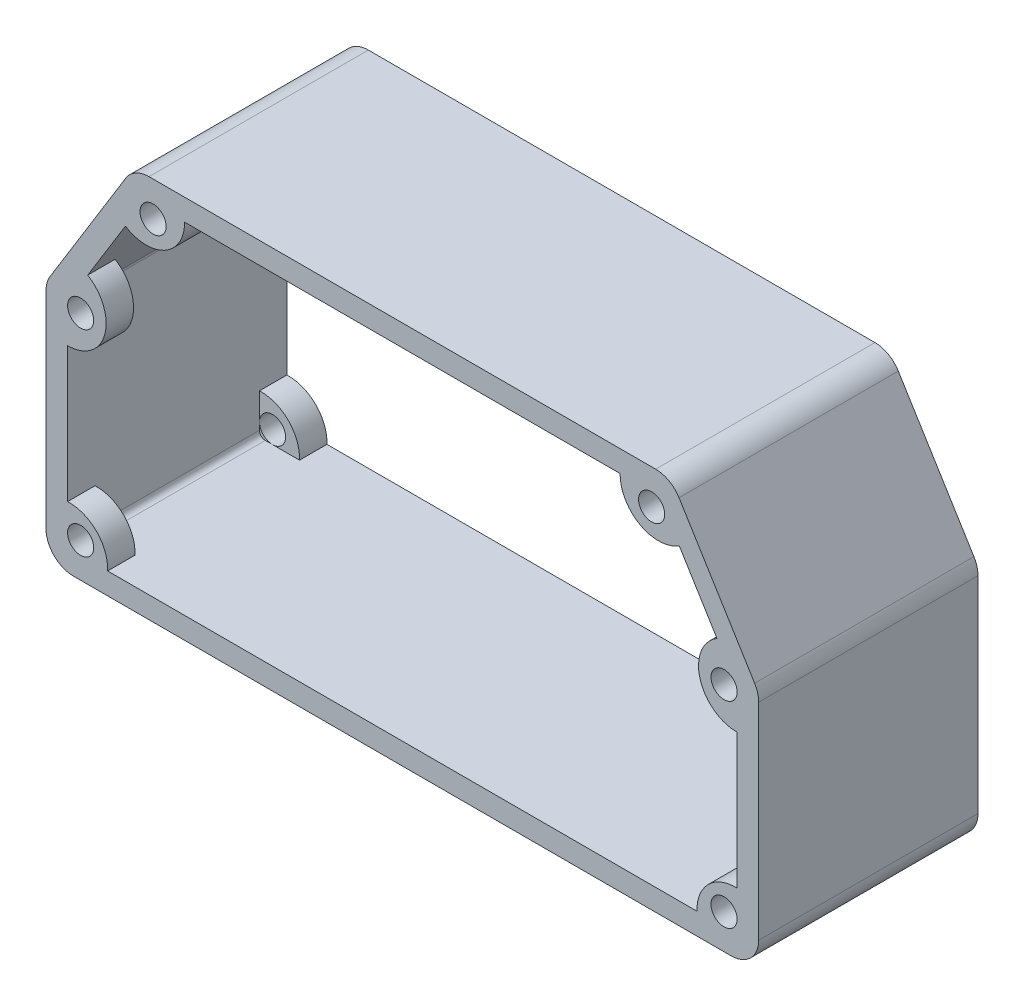
SolidWorks part; units mm, degrees
material "Custom Plastic"
ref_plane "X-Y Datum" through (0, 0, 0) normal (0, 0, 1) x (1, 0, 0)
ref_plane "X-Z Datum" through (0, 0, 0) normal (0, 1, 0) x (1, 0, 0)
ref_plane "Y-Z Datum" through (0, 0, 0) normal (1, 0, 0) x (0, 0, -1)
sketch "Sketch1" plane through (0, 0, 0) normal (0, 0, 1) x (1, 0, 0)
  line L0 (-82.55, -44.45) -> (-75.1791, 44.45)
  line L1 (-82.55, 44.45) -> (82.55, 44.45)
  line L2 (-82.55, 44.45) -> (-82.55, -44.45)
  line L3 (-82.55, -44.45) -> (82.55, -44.45)
  line L4 (82.55, 44.45) -> (82.55, -44.45)
  line L5 (-82.55, 44.45) -> (82.55, -44.45) construction
  line L6 (-82.55, -44.45) -> (82.55, 44.45) construction
  line L8 (0, 90.3576) -> (0, -90.3576) construction
  line L9 (82.55, -44.45) -> (75.1791, 44.45)
  point P0 (0, 0)
  point P12 (0, 0)
  dimension "D1" = 165.1
  dimension "D2" = 88.9
extrude "Boss-Extrude1" add sketch "Sketch1" along normal blind 50.8 contours L3 L9 L1 L0 | L1 L2 L0 | L9 L4 L1 region at (-80.093, 14.8167, 0) region at (0, -0.6924, 0) region at (80.093, 14.8167, 0)
sketch "Sketch2" plane through (0, 0, 0) normal (0, 0, -1) x (-1, 0, 0)
  line L0 (-82.55, 11.43) -> (-62.23, 44.45)
  line L1 (-82.55, 44.45) -> (-82.55, -44.45) construction
  line L2 (82.55, 44.45) -> (-82.55, 44.45) construction
  line L3 (0, -14.0019) -> (0, 14.0019) construction
  line L4 (82.55, 11.43) -> (62.23, 44.45)
  point P11 (0, 0)
  line M3 (-82.55, 44.45) -> (-82.55, -44.45)
  line M5 (82.55, -44.45) -> (82.55, 44.45)
  line M6 (82.55, 44.45) -> (-82.55, 44.45)
  dimension "D1" = 55.88
  dimension "D2" = 20.32
extrude "Cut-Extrude1" cut sketch "Sketch2" against normal through all contours L0 M3 M6 | L4 M5 M6 region at (75.7767, 33.4433, 0) region at (-75.7767, 33.4433, 0)
fillet "Fillet1" radius 6.35 6 edges at (82.55, -44.45, 25.4) (82.55, 11.43, 25.4) (62.23, 44.45, 25.4) (-62.23, 44.45, 25.4) (-82.55, 11.43, 25.4) (-82.55, -44.45, 25.4)
shell "Shell1" thickness 5 removed face at (0, 4.2293, 0)
sketch "Sketch4" plane through (0, 0, 45.8) normal (0, 0, -1) x (-1, 0, 0)
  line L6 (-59.8314, 38.8075) -> (-77.3497, 10.3402)
  line L7 (-77.55, 9.6327) -> (-77.55, -38.1)
  line L8 (-76.2, -39.45) -> (76.2, -39.45)
  line L9 (77.55, -38.1) -> (77.55, 9.6327)
  line L10 (77.3497, 10.3402) -> (59.8314, 38.8075)
  line L11 (58.6817, 39.45) -> (-58.6817, 39.45)
  line L12 (-59.8314, 38.8075) -> (-77.3497, 10.3402)
  line L13 (-77.55, 9.6327) -> (-77.55, -38.1)
  line L14 (-76.2, -39.45) -> (76.2, -39.45)
  line L15 (77.55, -38.1) -> (77.55, 9.6327)
  line L16 (77.3497, 10.3402) -> (59.8314, 38.8075)
  line L17 (58.6817, 39.45) -> (-58.6817, 39.45)
  arc A6 (76.2, -39.45) -> (77.55, -38.1) centre (76.2, -38.1) ccw
  arc A7 (76.2, -39.45) -> (77.55, -38.1) centre (76.2, -38.1) ccw
  arc A8 (77.55, 9.6327) -> (77.3497, 10.3402) centre (76.2, 9.6327) ccw
  arc A9 (77.55, 9.6327) -> (77.3497, 10.3402) centre (76.2, 9.6327) ccw
  arc A10 (59.8314, 38.8075) -> (58.6817, 39.45) centre (58.6817, 38.1) ccw
  arc A11 (59.8314, 38.8075) -> (58.6817, 39.45) centre (58.6817, 38.1) ccw
  arc A12 (-58.6817, 39.45) -> (-59.8314, 38.8075) centre (-58.6817, 38.1) ccw
  arc A13 (-58.6817, 39.45) -> (-59.8314, 38.8075) centre (-58.6817, 38.1) ccw
  arc A14 (-77.3497, 10.3402) -> (-77.55, 9.6327) centre (-76.2, 9.6327) ccw
  arc A15 (-77.3497, 10.3402) -> (-77.55, 9.6327) centre (-76.2, 9.6327) ccw
  arc A16 (-77.55, -38.1) -> (-76.2, -39.45) centre (-76.2, -38.1) ccw
  arc A17 (-77.55, -38.1) -> (-76.2, -39.45) centre (-76.2, -38.1) ccw
  dimension "D1" = 0
extrude "Cut-Extrude2" cut sketch "Sketch4" against normal through all
sketch "Sketch5" plane through (0, 0, 50.8) normal (0, 0, 1) x (1, 0, 0)
  line L0 (-77.55, -38.1) -> (-77.55, 9.6327) construction
  line L1 (76.2, -39.45) -> (-76.2, -39.45) construction
  line L6 (-68.2734, -39.45) -> (-76.2, -39.45)
  line L7 (-77.55, -30.1734) -> (-77.55, -38.1)
  line L8 (0, 0) -> (0, 50000) construction
  line L9 (77.55, -30.1734) -> (77.55, -38.1)
  line L10 (68.2734, -39.45) -> (76.2, -39.45)
  line L11 (59.8314, 38.8075) -> (77.3497, 10.3402) construction
  line L12 (77.55, 9.6327) -> (77.55, -38.1) construction
  line L14 (72.8833, 17.5982) -> (77.3497, 10.3402)
  line L15 (77.55, 9.6327) -> (77.55, 1.1105)
  line L16 (-72.8833, 17.5982) -> (-77.3497, 10.3402)
  line L17 (-77.55, 9.6327) -> (-77.55, 1.1105)
  line L18 (-58.6817, 39.45) -> (58.6817, 39.45) construction
  line L19 (-77.3497, 10.3402) -> (-59.8314, 38.8075) construction
  line L20 (-50.4518, 39.45) -> (-58.6817, 39.45)
  line L21 (-59.8314, 38.8075) -> (-64.1446, 31.7985)
  line L22 (59.8314, 38.8075) -> (64.1446, 31.7985)
  line L23 (50.4518, 39.45) -> (58.6817, 39.45)
  arc A0 (-77.55, -30.1734) -> (-68.2734, -39.45) centre (-77.1546, -39.0546) cw
  arc A1 (-77.55, -38.1) -> (-76.2, -39.45) centre (-76.2, -38.1) ccw construction
  arc A6 (77.55, -38.1) -> (76.2, -39.45) centre (76.2, -38.1) cw
  arc A7 (-77.55, -38.1) -> (-76.2, -39.45) centre (-76.2, -38.1) ccw
  arc A8 (-77.55, -38.1) -> (-76.2, -39.45) centre (-76.2, -38.1) ccw
  arc A9 (77.55, -30.1734) -> (68.2734, -39.45) centre (77.1546, -39.0546) ccw
  arc A10 (72.8833, 17.5982) -> (77.55, 1.1105) centre (77.499, 10.0003) ccw
  arc A11 (77.55, 9.6327) -> (77.3497, 10.3402) centre (76.2, 9.6327) ccw construction
  arc A12 (72.8833, 17.5982) -> (77.55, 1.1105) centre (77.499, 10.0003) ccw
  arc A14 (-77.55, 9.6327) -> (-77.3497, 10.3402) centre (-76.2, 9.6327) cw
  arc A15 (77.55, 9.6327) -> (77.3497, 10.3402) centre (76.2, 9.6327) ccw
  arc A16 (77.55, 9.6327) -> (77.3497, 10.3402) centre (76.2, 9.6327) ccw
  arc A17 (-72.8833, 17.5982) -> (-77.55, 1.1105) centre (-77.499, 10.0003) cw
  arc A18 (-72.8833, 17.5982) -> (-77.55, 1.1105) centre (-77.499, 10.0003) cw
  arc A20 (-50.4518, 39.45) -> (-64.1446, 31.7985) centre (-59.3402, 39.2785) cw
  arc A21 (-58.6817, 39.45) -> (-59.8314, 38.8075) centre (-58.6817, 38.1) ccw
  arc A22 (-58.6817, 39.45) -> (-59.8314, 38.8075) centre (-58.6817, 38.1) ccw
  arc A23 (58.6817, 39.45) -> (59.8314, 38.8075) centre (58.6817, 38.1) cw
  arc A24 (50.4518, 39.45) -> (64.1446, 31.7985) centre (59.3402, 39.2785) ccw
  arc M2 (77.3497, 10.3402) -> (77.55, 9.6327) centre (76.2, 9.6327) cw
  line M3 (77.55, 9.6327) -> (77.55, -38.1)
  arc M4 (77.55, -38.1) -> (76.2, -39.45) centre (76.2, -38.1) cw
  line M5 (76.2, -39.45) -> (-76.2, -39.45)
  arc M6 (-76.2, -39.45) -> (-77.55, -38.1) centre (-76.2, -38.1) cw
  line M7 (-77.55, -38.1) -> (-77.55, 9.6327)
  arc M8 (-77.55, 9.6327) -> (-77.3497, 10.3402) centre (-76.2, 9.6327) cw
  line M9 (-77.3497, 10.3402) -> (-59.8314, 38.8075)
  arc M10 (-59.8314, 38.8075) -> (-58.6817, 39.45) centre (-58.6817, 38.1) cw
  line M11 (-58.6817, 39.45) -> (58.6817, 39.45)
  arc M12 (58.6817, 39.45) -> (59.8314, 38.8075) centre (58.6817, 38.1) cw
  line M13 (59.8314, 38.8075) -> (77.3497, 10.3402)
  dimension "D2" = 0
  dimension "D4" = 8.89
  dimension "D5" = 8.89
  dimension "D6" = 8.89
  dimension "D1" = 0
  dimension "D3" = 0
extrude "Boss-Extrude2" add sketch "Sketch5" against normal blind 6.35 contours A0 M7 M6 M5 | A17 M9 M8 M7 | A20 M11 M10 M9 | A24 M11 M13 M12 | A10 M13 M3 M2 | A9 M3 M5 M4 region at (-73.537, -35.437, 50.8) region at (73.537, -35.437, 50.8) region at (-73.2884, 8.8086, 50.8) region at (73.2884, 8.8086, 50.8) region at (-57.0077, 35.1043, 50.8) region at (57.0077, 35.1043, 50.8)
ref_plane "Plane1" through (0, 0, 0) normal (1, 0, 0) x (0, 0, -1)
ref_plane "Plane2" through (0, 0, 25.4) normal (0, 0, 1) x (1, 0, 0)
mirror "Mirror1" about plane through (0, 0, 25.4) normal (0, 0, 1) of "Boss-Extrude2"
sketch "Sketch6" plane through (0, 0, 0) normal (0, 0, -1) x (-1, 0, 0)
  line L0 (0, 0) -> (0, -50000) construction
  line L1 (68.2734, -39.45) -> (-68.2734, -39.45) construction
  line L2 (77.55, 1.1105) -> (77.55, -30.1734) construction
  line L3 (72.8833, 17.5982) -> (64.1446, 31.7985) construction
  line L4 (50.4518, 39.45) -> (-50.4518, 39.45) construction
  line L5 (-52.15, 33.0406) -> (51.85, 33.0406) construction
  circle A1 centre (74.525, -36.425) radius 3.025
  circle A2 centre (74.525, 9.1586) radius 3.025
  circle A3 centre (57.7457, 36.425) radius 3.025
  circle A4 centre (-57.7457, 36.425) radius 3.025
  circle A5 centre (-74.525, 9.1586) radius 3.025
  circle A6 centre (-74.525, -36.425) radius 3.025
  point P11 (0, 0)
  point P14 (-0.15, 33.0406)
  point P19 (0, 0)
  point P20 (0, 0)
  point P21 (0, 0)
  point P22 (0, 0)
  point P23 (0, 0)
  point P24 (0, 0)
  dimension "D1" = 6.05
  dimension "D2" = 6.05
  dimension "D3" = 6.05
extrude "Cut-Extrude3" cut sketch "Sketch6" against normal through all both and the other way through all
sketch "Sketch7" plane through (0, 0, 0) normal (0, 0, 1) x (1, 0, 0)
  line L6 (-76.2, -40.64) -> (76.2, -40.64)
  line L7 (78.74, -38.1) -> (78.74, 9.6327)
  line L8 (78.3632, 10.9639) -> (60.8449, 39.4312)
  line L9 (58.6817, 40.64) -> (-58.6817, 40.64)
  line L10 (-60.8449, 39.4312) -> (-78.3632, 10.9639)
  line L11 (-78.74, 9.6327) -> (-78.74, -38.1)
  line L12 (-76.2, -43.18) -> (76.2, -43.18)
  line L13 (81.28, -38.1) -> (81.28, 9.6327)
  line L14 (80.5264, 12.2951) -> (63.0081, 40.7624)
  line L15 (58.6817, 43.18) -> (-58.6817, 43.18)
  line L16 (-63.0081, 40.7624) -> (-80.5264, 12.2951)
  line L17 (-81.28, 9.6327) -> (-81.28, -38.1)
  line L18 (-76.2, -43.18) -> (76.2, -43.18)
  line L19 (81.28, -38.1) -> (81.28, 9.6327)
  line L20 (80.5264, 12.2951) -> (63.0081, 40.7624)
  line L21 (58.6817, 43.18) -> (-58.6817, 43.18)
  line L22 (-63.0081, 40.7624) -> (-80.5264, 12.2951)
  line L23 (-81.28, 9.6327) -> (-81.28, -38.1)
  arc A6 (76.2, -40.64) -> (78.74, -38.1) centre (76.2, -38.1) ccw
  arc A7 (78.74, 9.6327) -> (78.3632, 10.9639) centre (76.2, 9.6327) ccw
  arc A8 (60.8449, 39.4312) -> (58.6817, 40.64) centre (58.6817, 38.1) ccw
  arc A9 (-58.6817, 40.64) -> (-60.8449, 39.4312) centre (-58.6817, 38.1) ccw
  arc A10 (-78.3632, 10.9639) -> (-78.74, 9.6327) centre (-76.2, 9.6327) ccw
  arc A11 (-78.74, -38.1) -> (-76.2, -40.64) centre (-76.2, -38.1) ccw
  arc A12 (76.2, -43.18) -> (81.28, -38.1) centre (76.2, -38.1) ccw
  arc A13 (81.28, 9.6327) -> (80.5264, 12.2951) centre (76.2, 9.6327) ccw
  arc A14 (63.0081, 40.7624) -> (58.6817, 43.18) centre (58.6817, 38.1) ccw
  arc A15 (-58.6817, 43.18) -> (-63.0081, 40.7624) centre (-58.6817, 38.1) ccw
  arc A16 (-80.5264, 12.2951) -> (-81.28, 9.6327) centre (-76.2, 9.6327) ccw
  arc A17 (-81.28, -38.1) -> (-76.2, -43.18) centre (-76.2, -38.1) ccw
  arc A18 (76.2, -43.18) -> (81.28, -38.1) centre (76.2, -38.1) ccw
  arc A19 (81.28, 9.6327) -> (80.5264, 12.2951) centre (76.2, 9.6327) ccw
  arc A20 (63.0081, 40.7624) -> (58.6817, 43.18) centre (58.6817, 38.1) ccw
  arc A21 (-58.6817, 43.18) -> (-63.0081, 40.7624) centre (-58.6817, 38.1) ccw
  arc A22 (-80.5264, 12.2951) -> (-81.28, 9.6327) centre (-76.2, 9.6327) ccw
  arc A23 (-81.28, -38.1) -> (-76.2, -43.18) centre (-76.2, -38.1) ccw
  dimension "D1" = 1.27
  dimension "D2" = 2.54
extrude "Cut-Extrude4" cut sketch "Sketch7" along normal blind 1.27
